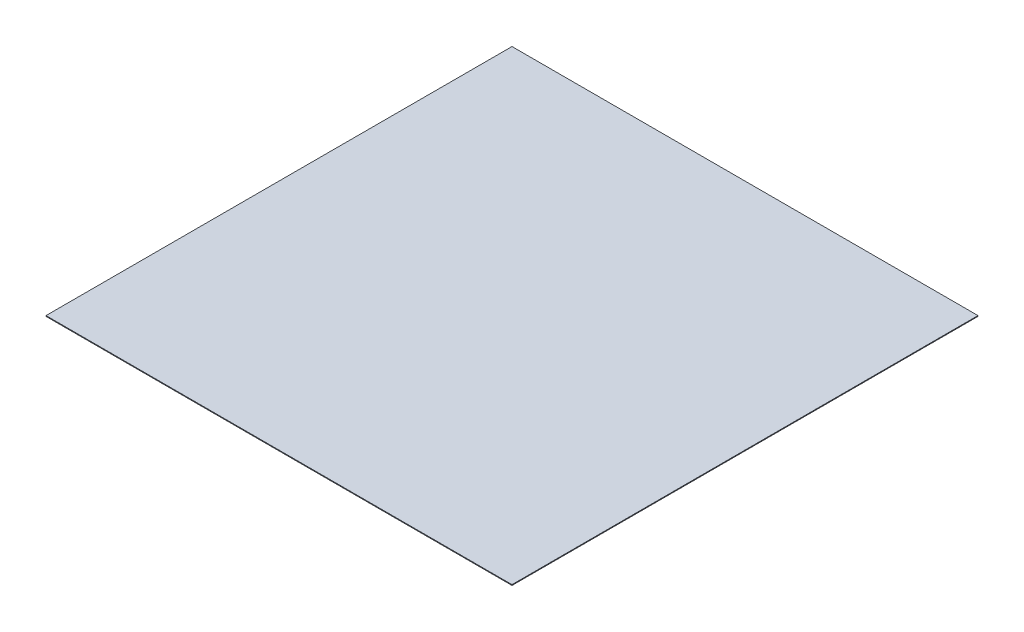
SolidWorks part; units mm, degrees
material "6061-T6 (SS)"
ref_plane "Front Plane" through (0, 0, 0) normal (0, 0, 1) x (1, 0, 0)
ref_plane "Top Plane" through (0, 0, 0) normal (0, 1, 0) x (1, 0, 0)
ref_plane "Right Plane" through (0, 0, 0) normal (1, 0, 0) x (0, 0, -1)
sketch "Sketch1" plane through (0, 0, 0) normal (0, 1, 0) x (1, 0, 0)
  line L1 (0, 0) -> (2000, 0)
  line L2 (0, 0) -> (0, -2000)
  line L3 (0, -2000) -> (2000, -2000)
  line L4 (2000, 0) -> (2000, -2000)
  dimension "D1" = 2000
  dimension "D2" = 2000
extrude "Boss-Extrude1" add sketch "Sketch1" along normal blind 3.175
sketch "Sketch3" plane through (0, 0, 0) normal (0, -1, 0) x (1, 0, 0)
  line L0 (0, 2000) -> (2000, 0) construction
  line L1 (0, 0) -> (2000, 2000) construction
  line L3 (2000, 0) -> (0, 0) construction
  line L5 (2000, 2000) -> (2000, 0) construction
  line L7 (0, 0) -> (0, 2000) construction
  line L9 (0, 2000) -> (2000, 2000) construction
  line L10 (1000, 500) -> (1000, 0) construction
  line L11 (1500, 1000) -> (2000, 1000)
  line L12 (500, 1000) -> (0, 1000)
  line L13 (1000, 1500) -> (1000, 2000)
  point P8 (1000, 1000)
  point P9 (1000, 250)
  point P13 (1000, 500)
  point P23 (1500, 1000)
  point P24 (500, 1000)
  point P25 (1000, 1500)
  point P30 (250, 1000)
  point P31 (1000, 1750)
  point P32 (1750, 1000)
